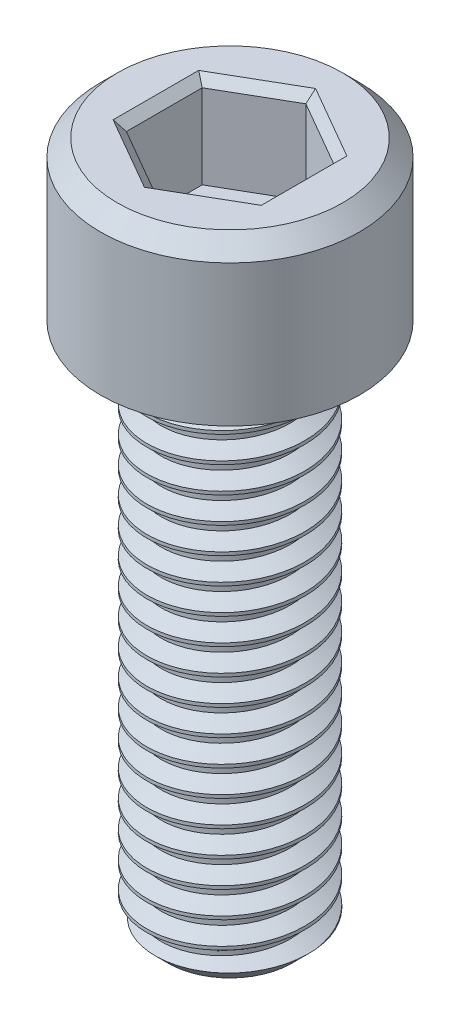
SolidWorks part; units mm, degrees
material "Plain Carbon Steel"
ref_plane "Front Plane" through (0, 0, 0) normal (0, 0, 1) x (1, 0, 0)
ref_plane "Top Plane" through (0, 0, 0) normal (0, 1, 0) x (1, 0, 0)
ref_plane "Right Plane" through (0, 0, 0) normal (1, 0, 0) x (0, 0, -1)
ref_plane "Plane1" through (0, 0, 0) normal (0, 0, -1) x (-1, 0, 0)
sketch "Sketch1" plane through (0, 0, 0) normal (0, 0, -1) x (-1, 0, 0)
  line L0 (-3.9116, -4.7752) -> (0, -4.7752)
  line L1 (0, -4.7752) -> (0, 0)
  line L2 (0, 0) -> (-3.9116, 0)
  line L3 (-3.9116, 0) -> (-3.9116, -4.7752)
  line L4 (0, -4.7752) -> (0, 0) construction
revolve "Revolve1" add sketch "Sketch1" angle 360 about L4 reverse direction yes
sketch "Sketch2" plane through (0, -4.7752, 0) normal (0, -1, 0) x (1, 0, 0)
  circle A0 centre (0, 0) radius 2.3876
extrude "Boss-Extrude1" add sketch "Sketch2" along normal blind 15.875
sketch "Sketch3" plane through (0, 0, 0) normal (0, 1, 0) x (-1, 0, 0)
  line L0 (1.9844, -1.1457) -> (1.9844, 1.1457)
  line L1 (1.9844, 1.1457) -> (0, 2.2914)
  line L2 (0, 2.2914) -> (-1.9844, 1.1457)
  line L3 (-1.9844, 1.1457) -> (-1.9844, -1.1457)
  line L4 (-1.9844, -1.1457) -> (0, -2.2914)
  line L5 (0, -2.2914) -> (1.9844, -1.1457)
extrude "Cut-Extrude1" cut sketch "Sketch3" against normal blind 2.794
chamfer "Chamfer1" distance 0.508 angle 45 2 edges at (0, -20.6502, -2.3876) (0, 0, 3.9116)
chamfer "Chamfer2" distance 0.254 angle 45 6 edges at (-0.9922, 0, -1.7185) (-1.9844, 0, 0) (0.9922, 0, -1.7185) (-0.9922, 0, 1.7185) (1.9844, 0, 0) (0.9922, 0, 1.7185)
thread "Thread1" pitch 0.7937 method cut profile "Thread Profile1" start angle 0, offset 0, length 0, pitch 0.7937, diameter 4.7752
ref_plane "Plane2" through (-2.3876, -4.7752, 0) normal (0, 0, 1) x (-1, 0, 0)
sketch "Thread Profile1" plane through (-2.3876, -4.7752, 0) normal (0, 0, 1) x (-1, 0, 0)
  line L0 (0, 0) -> (0, 0.7937) construction
  line L11 (0, 0) -> (0, 0.6945)
  line L12 (0, 0.6945) -> (-0.4296, 0.4465)
  line L13 (-0.4296, 0.4465) -> (-0.4296, 0.248)
  line L15 (-0.4296, 0.248) -> (0, 0)
  line L17 (-0.4296, 0.3473) -> (0, 0.3473) construction
  point P2 (0, 0)
  dimension "Pitch" = 0.7937
  dimension "Profile_Angle" = 60
  dimension "Profile_Land" = 0.1984
  dimension "Profile_Height" = 0.4296
